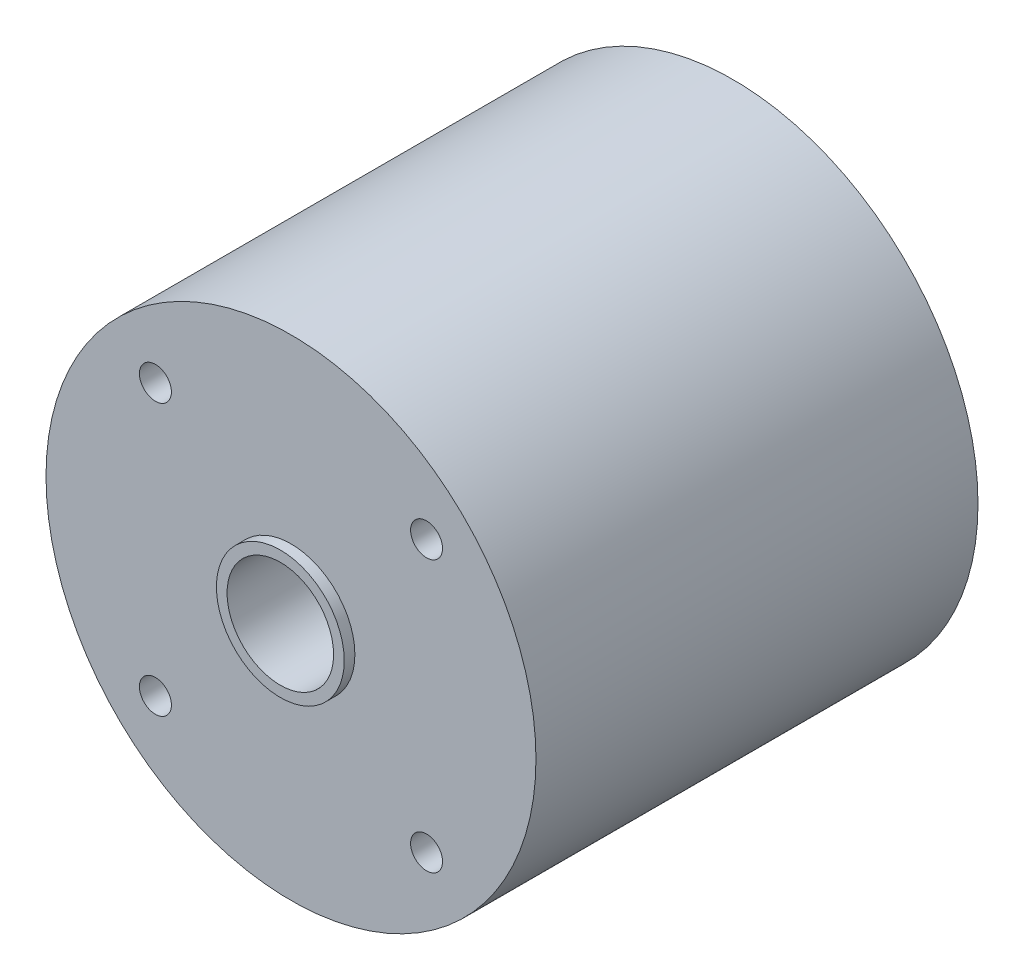
SolidWorks part; units mm, degrees
ref_plane "Ön Düzlem" through (0, 0, 0) normal (0, 0, 1) x (1, 0, 0)
ref_plane "Üst Düzlem" through (0, 0, 0) normal (0, 1, 0) x (1, 0, 0)
ref_plane "Sağ Düzlem" through (0, 0, 0) normal (1, 0, 0) x (0, 0, -1)
sketch "Çizim1" plane through (0, 0, 0) normal (0, 0, 1) x (1, 0, 0)
  circle A0 centre (0, 0) radius 46
  circle A1 centre (0, 0) radius 12
  circle A2 centre (0, 0) radius 10
  dimension "D1" = 92
  dimension "D2" = 24
  dimension "D3" = 20
extrude "Yükseklik-Ekstrüzyon2" add sketch "Çizim1" against normal blind 83 contours A0 A1 | A1 A2 region at (-44.6989, 0, 0) region at (-11.6606, 0, 0)
extrude "Yükseklik-Ekstrüzyon3" add sketch "Çizim1<4>" along normal blind 2 contours A1 A2 region at (-11.6606, 0, 0)
sketch "Çizim1<4>" plane through (0, 0, 0) normal (0, 0, 1) x (1, 0, 0) same geometry as "Çizim1"
extrude "Yükseklik-Ekstrüzyon4" add sketch "Çizim1<7>" against normal blind 2 from surface contours A1 A2 region at (-11.6606, 0, 0) starting at face at (46, 0, -83)
sketch "Çizim1<7>" plane through (0, 0, 0) normal (0, 0, 1) x (1, 0, 0) same geometry as "Çizim1"
sketch "Çizim2" plane through (0, 0, 0) normal (0, 0, 1) x (1, 0, 0)
  line L0 (0, 36) -> (0, 0) construction
  line L1 (0, 0) -> (-25.4558, 25.4558) construction
  circle A0 centre (0, 0) radius 36 construction
  circle A1 centre (-25.4558, 25.4558) radius 3
  circle A2 centre (25.4558, 25.4558) radius 3
  circle A3 centre (25.4558, -25.4558) radius 3
  circle A4 centre (-25.4558, -25.4558) radius 3
  circle A5 centre (0, 0) radius 12 construction
  dimension "D1" = 72
  dimension "D3" = 6
  dimension "D2" = 45
  dimension "D4" = 4
extrude "Kes-Ekstrüzyon1" cut sketch "Çizim2" against normal blind 100
